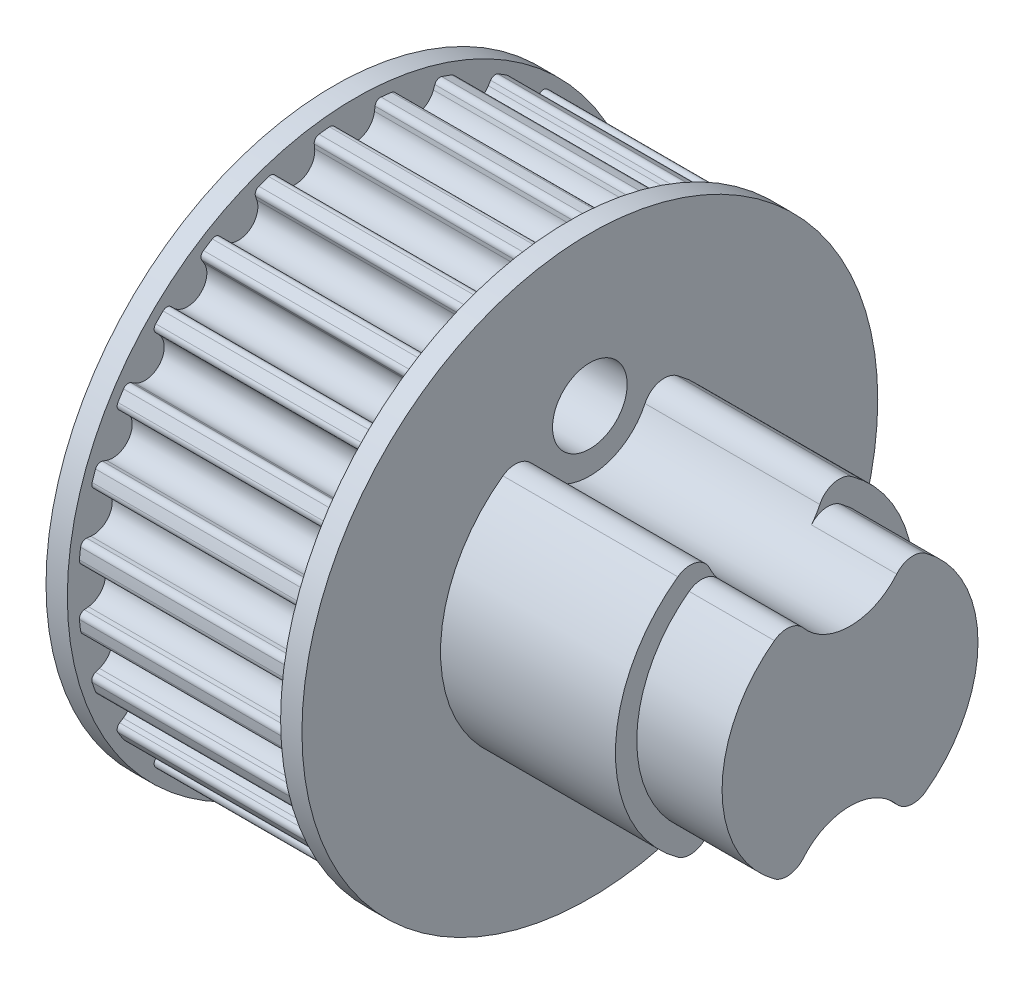
SolidWorks part; units mm, degrees
material "玻纤增强尼龙1010"
ref_plane "前视基准面" through (0, 0, 0) normal (0, 0, 1) x (1, 0, 0)
ref_plane "上视基准面" through (0, 0, 0) normal (0, 1, 0) x (1, 0, 0)
ref_plane "右视基准面" through (0, 0, 0) normal (1, 0, 0) x (0, 0, -1)
sketch "草图1" plane through (0, 0, 0) normal (0, 0, 1) x (1, 0, 0)
  line L0 (0, 0) -> (64.8368, 0) construction
  line L1 (0, 2.5978) -> (0, 12.989)
  line L2 (0, 12.989) -> (10, 12.989)
  line L3 (10, 12.989) -> (10, 5.1956)
  line L4 (10, 5.1956) -> (10.8, 5.1956)
  line L5 (10.8, 5.1956) -> (10.8, 2.5978)
  line L6 (10.8, 2.5978) -> (0, 2.5978)
  dimension "L" = 10.8
  dimension "B" = 10
  dimension "d" = 5.1956
  dimension "d1" = 10.3912
  dimension "da" = 25.978
revolve "旋转1" add sketch "草图1" angle 360 about L0
ref_axis "基准轴1" through (-0.54, 0, 0) along (1, 0, 0)
sketch "草图6" plane through (0, 0, 0) normal (1, 0, 0) x (0, 0, -1)
  line L0 (0, 0) -> (0, 30.6512) construction
  line L1 (0.9274, 12.7054) -> (0.9032, 12.5081)
  line L2 (1.4683, 12.9057) -> (1.665, 14.5073)
  line L3 (-1.4683, 12.9057) -> (-1.665, 14.5073)
  line L4 (-0.9274, 12.7054) -> (-0.9032, 12.5081)
  circle A0 centre (0, 0) radius 12.989 construction
  circle A1 centre (0, 0) radius 11.709 construction
  arc A2 (-0.9032, 12.5081) -> (0.9032, 12.5081) centre (0, 12.619) ccw
  arc A3 (1.665, 14.5073) -> (-1.665, 14.5073) centre (0, 0) ccw
  arc A4 (0.9274, 12.7054) -> (1.2097, 12.9325) centre (1.1855, 12.6737) cw
  arc A5 (1.2097, 12.9325) -> (1.4683, 12.9057) centre (0, 0) cw
  arc A6 (-1.2097, 12.9325) -> (-1.4683, 12.9057) centre (0, 0) ccw
  arc A7 (-0.9274, 12.7054) -> (-1.2097, 12.9325) centre (-1.1855, 12.6737) ccw
  point P7 (0, 1.9)
  point P8 (0, 29.3712)
  point P15 (0.9579, 12.9536)
  dimension "D1" = 23.418
  dimension "ra" = 0.26
  dimension "rf" = 0.91
  dimension "hg" = 1.28
  dimension "D3" = 0.26
  dimension "D4" = 1.6136
  dimension "angle" = 14
  dimension "bw" = 1.9
extrude "切除-拉伸2" cut sketch "草图6" along normal up to next
pattern_circular "阵列(圆周)3" count 28 over 360 about axis through (-0.54, 0, 0) along (1, 0, 0) of "切除-拉伸2"
sketch "草图7" plane through (0, 0, 0) normal (-1, 0, 0) x (0, 0, 1)
  circle A0 centre (0, 0) radius 2.5978
extrude "凸台-拉伸1" add sketch "草图7" against normal up to surface (10.8 mm away) up to face at (10.8, 0, 5.1956)
sketch "草图8" plane through (0, 0, 0) normal (-1, 0, 0) x (0, 0, 1)
  circle A0 centre (0, 0) radius 13.5
  dimension "D1" = 27
extrude "凸台-拉伸2" add sketch "草图8" along normal blind 1
sketch "草图9" plane through (10, 0, 0) normal (1, 0, 0) x (0, 0, -1)
  circle A0 centre (0, 0) radius 13.5
extrude "凸台-拉伸3" add sketch "草图9" along normal blind 1
sketch "草图10" plane through (-1, 0, 0) normal (-1, 0, 0) x (0, 0, 1)
  circle A0 centre (0, 0) radius 9.5
  dimension "D1" = 19
extrude "切除-拉伸3" cut sketch "草图10" against normal blind 5
sketch "草图11" plane through (4, 0, 0) normal (-1, 0, 0) x (0, 0, 1)
  circle A0 centre (0, 0) radius 6.5 construction
  circle A1 centre (0, 6.5) radius 1.75
  circle A2 centre (0, -6.5) radius 1.6
  dimension "D1" = 13
  dimension "D2" = 3.5
  dimension "D3" = 3.2
extrude "切除-拉伸4" cut sketch "草图11" against normal blind 13
sketch "草图12" plane through (11, 0, 0) normal (1, 0, 0) x (0, 0, -1)
  circle A0 centre (0, 0) radius 7
  dimension "D1" = 14
extrude "凸台-拉伸4" add sketch "草图12" along normal blind 8.2
sketch "草图13" plane through (19.2, 0, 0) normal (1, 0, 0) x (0, 0, -1)
  circle A0 centre (0, 0) radius 6
  dimension "D1" = 12
extrude "凸台-拉伸5" add sketch "草图13" along normal blind 4
sketch "草图14" plane through (23.2, 0, 0) normal (1, 0, 0) x (0, 0, -1)
  circle A0 centre (0, 6.5) radius 2.85
  circle A1 centre (0, -6.5) radius 2.85
  dimension "D1" = 5.7
  dimension "D2" = 5.7
extrude "切除-拉伸5" cut sketch "草图14" against normal up to surface (12.2 mm away) up to face at (11, -0.0036, 0)
fillet "圆角2" radius 1 4 edges at (15.1, 6.3944, -2.848) (15.1, 6.3944, 2.848) (15.1, -6.3944, -2.848) (15.1, -6.3944, 2.848) tangent propagation no
fillet "圆角3" radius 1 4 edges at (21.2, -5.3913, -2.6333) (21.2, -5.3913, 2.6333) (21.2, 5.3913, -2.6333) (21.2, 5.3913, 2.6333)
equation "\"D1@草图6\" = \"da@草图1\"  - \"hg@草图6\" - \"hg@草图6\""
equation "\"D3@草图6\" = \"ra@草图6\""
